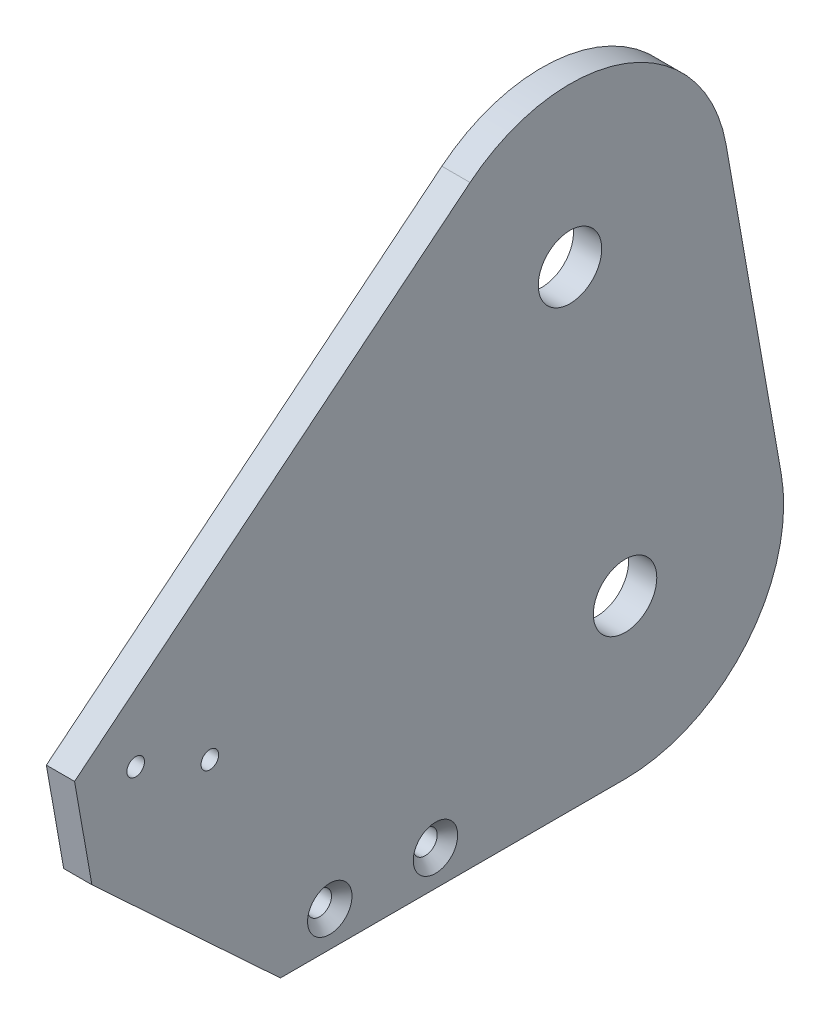
SolidWorks part; units mm, degrees
ref_plane "Front Plane" through (0, 0, 0) normal (0, 0, 1) x (1, 0, 0)
ref_plane "Top Plane" through (0, 0, 0) normal (0, 1, 0) x (1, 0, 0)
ref_plane "Right Plane" through (0, 0, 0) normal (1, 0, 0) x (0, 0, -1)
ref_plane "Plane1" through (25, 0, 0) normal (1, 0, 0) x (0, 0, -1)
sketch "Sketch2" plane through (25, 0, 0) normal (1, 0, 0) x (0, 0, -1)
  line L0 (41.2408, 127.9813) -> (49.0549, 83.6649)
  line L1 (26.8968, 57.2579) -> (-22, 57.2579)
  line L2 (-22, 57.2579) -> (-48.7484, 82.0825)
  line L3 (-48.7484, 82.0825) -> (-51.2055, 96.0176)
  line L4 (-51.2055, 96.0176) -> (4.9059, 141.5462)
  line L5 (-49.4393, 91.7596) -> (-49.8734, 94.2216) construction
  line L6 (-48.1109, 84.2258) -> (-46.6337, 84.4863) construction
  line L7 (-49.8734, 94.2216) -> (-48.3962, 94.4821) construction
  circle A0 centre (26.8968, 79.7579) radius 22.5 construction
  circle A1 centre (19.0826, 124.0742) radius 22.5 construction
  arc A2 (26.8968, 57.2579) -> (49.0549, 83.6649) centre (26.8968, 79.7579) ccw
  arc A3 (41.2408, 127.9813) -> (4.9059, 141.5462) centre (19.0826, 124.0742) ccw
  circle A4 centre (-15, 62.2579) radius 3.1263 construction
  circle A5 centre (0, 62.2579) radius 3.1263 construction
  dimension "D1" = 2
  dimension "D2" = 2
  dimension "D3" = 1
  dimension "D4" = 2
  dimension "D5" = 15
  dimension "D6" = 5
extrude "Boss-Extrude1" add sketch "Sketch2" along normal blind 4
hole_wizard "Hole1" positions "Sketch3" profile "Sketch4" legacy
sketch "Sketch3" plane through (25, 0, 0) normal (-1, 0, 0) x (0, 0, 1)
  point P0 (-19.0826, 124.0742)
  point P3 (-26.8968, 79.7579)
sketch "Sketch4" plane through (25, 124.0742, -19.0826) normal (0, 1, 0) x (0, 0, 1)
  line L0 (0, 0) -> (0, 100)
  line L1 (0, 100) -> (4.5, 100)
  line L2 (4.5, 100) -> (4.5, 0)
  line L3 (4.5, 0) -> (0, 0)
  line L4 (0, 110) -> (0, -10) construction
  dimension "Diameter" = 9
  dimension "Depth" = 100
hole_wizard "Hole2" positions "Sketch5" profile "Sketch6" legacy
sketch "Sketch5" plane through (25, 0, 0) normal (-1, 0, 0) x (0, 0, 1)
  point P0 (42.534, 93.4849)
  point P3 (32.0119, 89.0953)
sketch "Sketch6" plane through (25, 93.4849, 42.534) normal (0, 1, 0) x (0, 0, 1)
  line L0 (0, 0) -> (0, 100)
  line L1 (0, 100) -> (1.25, 100)
  line L2 (1.25, 100) -> (1.25, 0)
  line L3 (1.25, 0) -> (0, 0)
  line L4 (0, 110) -> (0, -10) construction
  dimension "Diameter" = 2.5
  dimension "Depth" = 100
hole_wizard "CSK for M3 Flat Head Machine Screw1" positions "Sketch9" profile "Sketch8" countersink size "M3" standard "ANSI Metric" end condition through all
sketch "Sketch9" plane through (29, 0, 0) normal (1, 0, 0) x (0, 0, -1)
  point P0 (0, 62.2579)
  point P3 (-15, 62.2579)
sketch "Sketch8" plane through (29, 62.2579, 0) normal (0, 1, 0) x (0, 0, -1)
  line L0 (0, 0) -> (0, 4)
  line L1 (0, 4) -> (1.7, 4)
  line L2 (1.7, 4) -> (1.7, 1.45)
  line L3 (1.7, 1.45) -> (3.15, 0)
  line L5 (3.15, 0) -> (0, 0)
  line L6 (-1.7, 1.45) -> (-3.15, 0) construction
  line L11 (0, -6.35) -> (0, 107.95) construction
  dimension "Thru Hole Dia." = 3.4
  dimension "Thru Hole Depth" = 4
  dimension "Near C'Sink Dia." = 6.3
  dimension "Near C'Sink Angle" = 90
